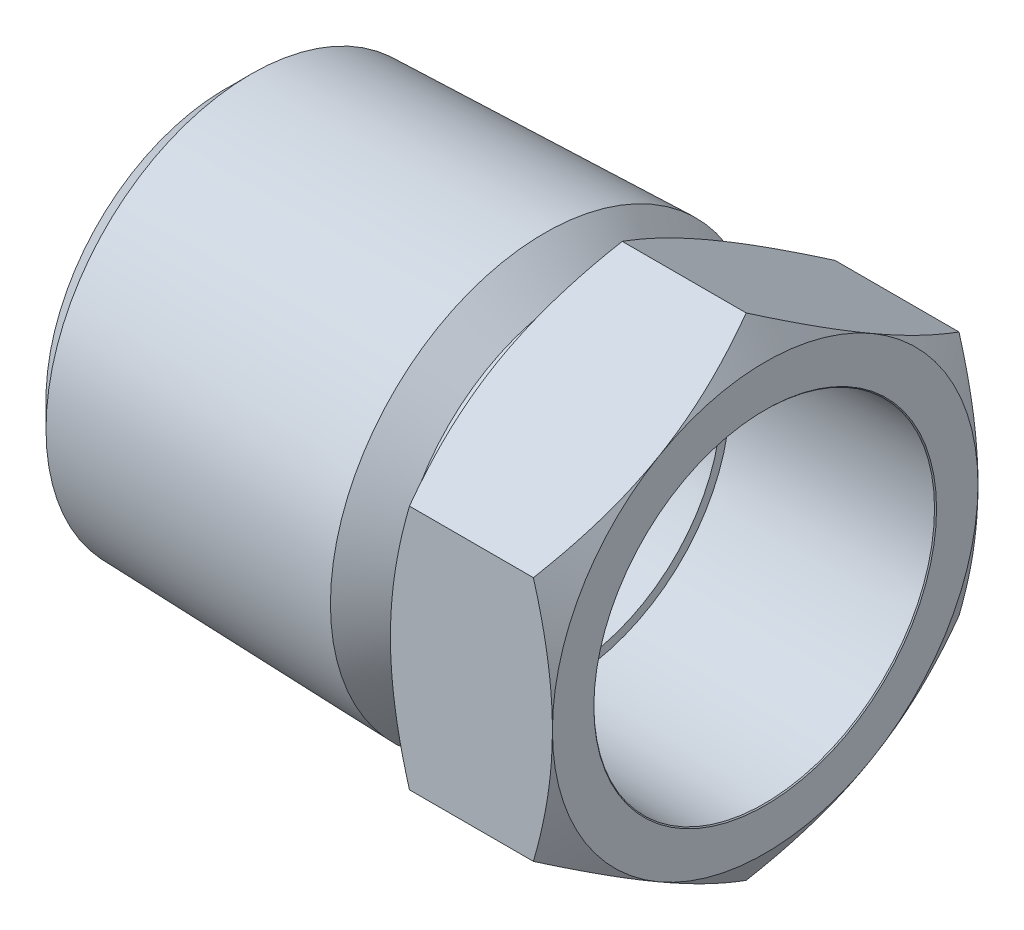
SolidWorks part; units mm, degrees
ref_plane "Front" through (0, 0, 0) normal (0, 0, 1) x (1, 0, 0)
ref_plane "Top" through (0, 0, 0) normal (0, 1, 0) x (1, 0, 0)
ref_plane "Right" through (0, 0, 0) normal (1, 0, 0) x (0, 0, -1)
sketch "Sketch1" plane through (0, 0, 0) normal (0, 0, 1) x (1, 0, 0)
  line L0 (-14.097, 0) -> (14.097, 0) construction
ref_plane "Plane1" through (-14.097, 0, 0) normal (1, 0, 0) x (0, 0, -1)
sketch "Sketch2" plane through (-14.097, 0, 0) normal (1, 0, 0) x (0, 0, -1)
  circle A0 centre (0, 0) radius 10.668
  dimension "OD" = 21.336
extrude "Extrude1" add sketch "Sketch2" along normal up to vertex (28.194 mm away) draft 1.783 up to point (14.097, 0, 0) draft outward yes
sketch "Sketch3" plane through (-14.097, 0, 0) normal (-1, 0, 0) x (0, 0, 1)
  circle A1 centre (0, 0) radius 10.668
  circle A2 centre (0, 0) radius 10.668
  dimension "D1" = 0
curve "Helix/Spiral1" parameters "pitch"=1.8143
sketch "Sketch4" plane through (0, 0, 0) normal (0, 0, 1) x (1, 0, 0)
  line L0 (-15.6845, 10.668) -> (-15.0041, 9.4896)
  line L1 (-15.0041, 9.4896) -> (-14.7774, 9.4896)
  line L2 (-14.7774, 9.4896) -> (-14.097, 10.668)
  line L3 (-15.6845, 10.668) -> (-14.097, 10.668) construction
  line L4 (-15.3443, 10.0788) -> (-14.4372, 10.0788) construction
  line L5 (-14.8907, 9.4896) -> (-14.8907, 10.668) construction
  line L6 (-15.6845, 10.668) -> (-13.9171, 10.9796)
  line L7 (-14.097, 10.668) -> (-13.9171, 10.9796)
  line L8 (-14.097, 10.668) -> (-14.097, -10.668) construction
  dimension "D1" = 10
  dimension "D2" = 0.2268
  dimension "D3" = 0.9071
  dimension "D4" = 60
sweep "Cut-Sweep1" [suppressed] cut profiles "Sketch4" path "Helix/Spiral1"
sketch "Sketch5" plane through (-14.097, 0, 0) normal (1, 0, 0) x (0, 0, -1)
  circle A0 centre (0, 0) radius 9.4896 construction
  circle A1 centre (0, 0) radius 9.3626
  dimension "D1" = 0.127
extrude "Cut-Extrude1" cut sketch "Sketch5" along normal through all draft 45 flip side to cut
ref_plane "Plane2" through (14.097, 0, 0) normal (1, 0, 0) x (0, 0, -1)
ref_plane "Plane3" through (5.6388, 0, 0) normal (1, 0, 0) x (0, 0, -1)
sketch "Sketch8" plane through (5.6388, 0, 0) normal (1, 0, 0) x (0, 0, -1)
  circle A2 centre (0, 0) radius 17.018
  circle A3 centre (0, 0) radius 17.018
  dimension "D1" = 6.35
extrude "Cut-Extrude4" cut sketch "Sketch8" along normal through all
sketch "Sketch9" plane through (5.6388, 0, 0) normal (1, 0, 0) x (0, 0, -1)
  circle A0 centre (0, 0) radius 10.668 construction
  circle A2 centre (0, 0) radius 9.4896
extrude "Cut-Extrude5" cut sketch "Sketch9" against normal blind 1.3607 flip side to cut
ref_plane "Plane4" through (4.2781, 0, 0) normal (1, 0, 0) x (0, 0, -1)
sketch "Sketch10" plane through (4.2781, 0, 0) normal (1, 0, 0) x (0, 0, -1)
  circle A1 centre (0, 0) radius 9.4896
  circle A2 centre (0, 0) radius 9.4896
  dimension "D1" = 0
extrude "Cut-Extrude6" cut sketch "Sketch10" against normal through all draft 45 flip side to cut
sketch "Sketch6" plane through (14.097, 0, 0) normal (1, 0, 0) x (0, 0, -1)
  line L1 (0, 12.8316) -> (-11.1125, 6.4158)
  line L2 (-11.1125, 6.4158) -> (-11.1125, -6.4158)
  line L3 (-11.1125, -6.4158) -> (0, -12.8316)
  line L4 (0, -12.8316) -> (11.1125, -6.4158)
  line L5 (11.1125, -6.4158) -> (11.1125, 6.4158)
  line L6 (11.1125, 6.4158) -> (0, 12.8316)
  circle A0 centre (0, 0) radius 11.1125 construction
  dimension "Hex" = 22.225
extrude "Extrude2" add sketch "Sketch6" against normal blind 8.4582
sketch "Sketch7" plane through (14.097, 0, 0) normal (1, 0, 0) x (0, 0, -1)
  line L0 (0, 12.8316) -> (-11.1125, 6.4158) construction
  circle A0 centre (0, 0) radius 11.1125
extrude "Cut-Extrude2" cut sketch "Sketch7" against normal through all draft 60 flip side to cut
sketch "Sketch18" plane through (5.6388, 0, 0) normal (-1, 0, 0) x (0, 0, 1)
  circle A0 centre (0, 0) radius 11.1125 construction
  circle A1 centre (0, 0) radius 11.1125
extrude "Extrude3" cut sketch "Sketch18" against normal blind 10 draft 60 flip side to cut
ref_plane "Plane5" through (3.683, 0, 0) normal (1, 0, 0) x (0, 0, -1)
sketch "Sketch11" plane through (3.683, 0, 0) normal (1, 0, 0) x (0, 0, -1)
  circle A0 centre (0, 0) radius 8.5725
  dimension "OD2" = 17.145
extrude "Cut-Extrude7" cut sketch "Sketch11" along normal through all draft 1.783 draft outward yes
sketch "Sketch12" plane through (3.683, 0, 0) normal (1, 0, 0) x (0, 0, -1)
  circle A0 centre (0, 0) radius 8.5725 construction
  circle A1 centre (0, 0) radius 8.5725
curve "Helix/Spiral2" parameters "pitch 2"=1.4111
sketch "Sketch16" plane through (14.097, 0, 0) normal (1, 0, 0) x (0, 0, -1)
  circle A2 centre (0, 0) radius 8.9475
  circle A3 centre (0, 0) radius 8.9475
  dimension "D1" = 0.0508
sketch "Sketch14" plane through (0, 0, 0) normal (0, 0, 1) x (1, 0, 0)
  line L0 (2.4483, 8.5725) -> (3.683, 8.5725) construction
  line L1 (3.683, 8.5725) -> (3.1538, 7.656) construction
  line L2 (3.1538, 7.656) -> (2.9774, 7.656)
  line L3 (2.9774, 7.656) -> (2.4483, 8.5725)
  line L4 (2.7129, 8.1142) -> (3.4184, 8.1142) construction
  line L5 (3.0656, 7.656) -> (3.0656, 8.5725) construction
  line L6 (2.4483, 8.5725) -> (3.8229, 8.8149)
  line L7 (3.8229, 8.8149) -> (3.1538, 7.656)
  line L8 (3.683, -8.5725) -> (3.683, 8.5725) construction
  dimension "D1" = 10
  dimension "D2" = 60
  dimension "D3" = 0.1764
  dimension "D4" = 0.7056
sweep "Sweep1" [suppressed] add profiles "Sketch14" path "Helix/Spiral2"
sketch "Sketch15" plane through (14.097, 0, 0) normal (1, 0, 0) x (0, 0, -1)
  line L6 (0, 12.8316) -> (-11.1125, 6.4158)
  line L7 (-11.1125, 6.4158) -> (-11.1125, -6.4158)
  line L8 (-11.1125, -6.4158) -> (0, -12.8316)
  line L9 (0, -12.8316) -> (11.1125, -6.4158)
  line L10 (11.1125, -6.4158) -> (11.1125, 6.4158)
  line L11 (11.1125, 6.4158) -> (0, 12.8316)
  line L12 (0, 12.8316) -> (-11.1125, 6.4158)
  line L13 (-11.1125, 6.4158) -> (-11.1125, -6.4158)
  line L14 (-11.1125, -6.4158) -> (0, -12.8316)
  line L15 (0, -12.8316) -> (11.1125, -6.4158)
  line L16 (11.1125, -6.4158) -> (11.1125, 6.4158)
  line L17 (11.1125, 6.4158) -> (0, 12.8316)
  dimension "D1" = 0
extrude "Cut-Extrude8" [suppressed] cut sketch "Sketch15" along normal through all
extrude "Cut-Extrude9" cut sketch "Sketch16" against normal blind 6.35 draft 45
sketch "Sketch17" plane through (0, 0, 0) normal (0, 0, 1) x (1, 0, 0)
  line L1 (-14.097, 8.1142) -> (3.683, 8.1142)
  line L2 (3.683, 8.1142) -> (3.683, 0)
  line L3 (3.683, 0) -> (-14.097, 0)
  line L4 (-14.097, 0) -> (-14.097, 8.1142)
  line L5 (-14.097, -10.668) -> (-14.097, 10.668) construction
  line L6 (3.683, -8.5725) -> (3.683, 8.5725) construction
revolve "Cut-Revolve1" cut sketch "Sketch17" angle 360 about L0
equation "\"D3@Helix/Spiral1\" = \"L@Sketch1\""
equation "\"D2@Sketch4\" = \"pitch@Helix/Spiral1\"*.125"
equation "\"D3@Sketch4\" = \"pitch@Helix/Spiral1\"*.5"
equation "\"D1@Extrude2\" = \"L@Sketch1\"*.3"
equation "\"D1@Plane3\" = \"D1@Extrude2\""
equation "\"D1@Cut-Extrude5\" = \"pitch@Helix/Spiral1\"*.75"
equation "\"D1@Plane4\" = \"D1@Cut-Extrude5\""
equation "\"D3@Helix/Spiral2\" = \"thread engagement @Plane5\"+.250"
equation "\"D3@Sketch14\" = \"pitch 2@Helix/Spiral2\"*.125"
equation "\"D4@Sketch14\" = \"pitch 2@Helix/Spiral2\"*.50"
